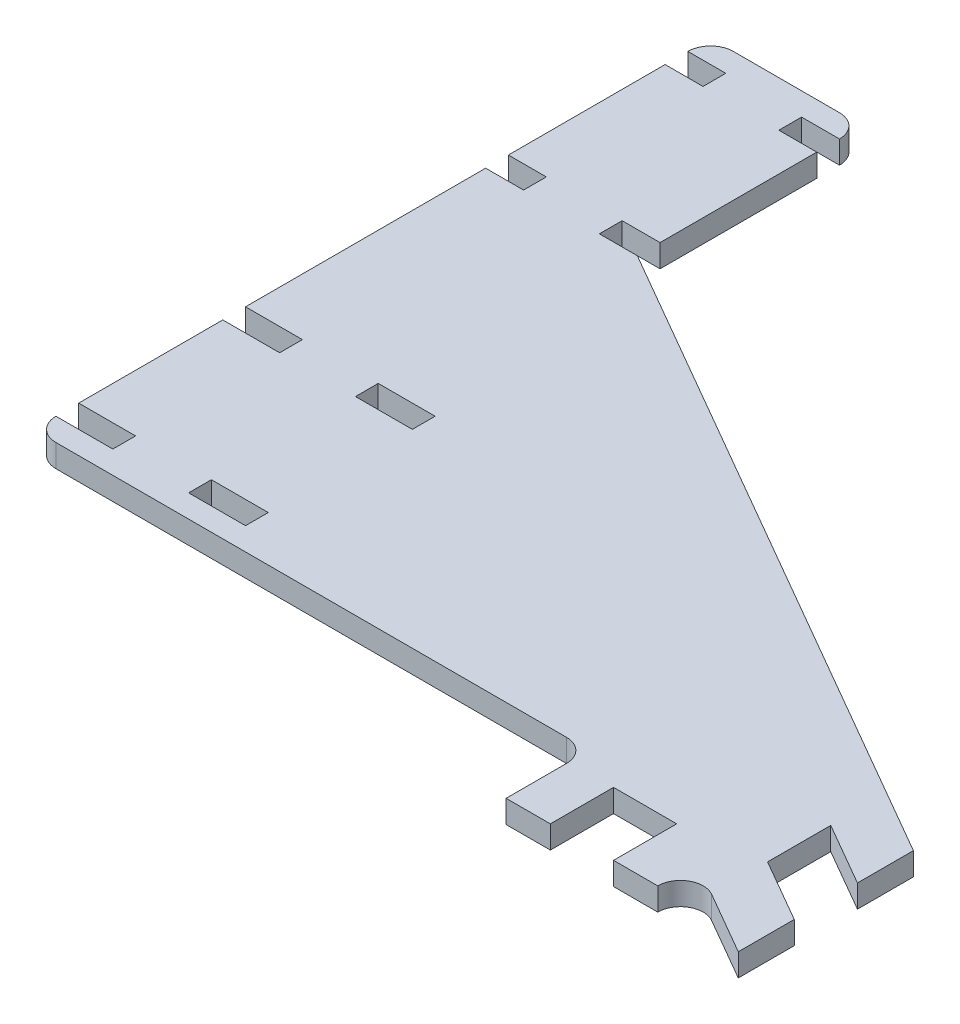
SolidWorks part; units mm, degrees
ref_plane "Front Plane" through (0, 0, 0) normal (0, 0, 1) x (1, 0, 0)
ref_plane "Top Plane" through (0, 0, 0) normal (0, 1, 0) x (1, 0, 0)
ref_plane "Right Plane" through (0, 0, 0) normal (1, 0, 0) x (0, 0, -1)
sketch "Sketch1" plane through (0, 0, 0) normal (0, 1, 0) x (1, 0, 0)
  line L0 (-363.1089, 480) -> (-363.1089, -480)
  line L1 (-363.1089, -480) -> (-303.1089, -480)
  line L2 (-303.1089, -480) -> (-303.1089, -400)
  line L3 (-303.1089, -400) -> (303.1089, -50)
  line L4 (303.1089, -50) -> (1036.8911, -50)
  line L5 (1036.8911, -50) -> (1036.8911, 50) construction
  line L6 (1036.8911, 50) -> (303.1089, 50)
  line L7 (303.1089, 50) -> (-303.1089, 400)
  line L8 (-303.1089, 400) -> (-303.1089, 480)
  line L9 (-303.1089, 480) -> (-363.1089, 480)
  line L10 (-363.1089, 0) -> (1036.8911, 0) construction
  line L11 (0, 225) -> (0, -225) construction
  line L14 (1036.8911, 50) -> (1066.8911, 50)
  line L15 (1036.8911, 50) -> (1036.8911, -50) construction
  line L16 (1036.8911, -50) -> (1066.8911, -50)
  line L17 (1066.8911, 50) -> (1066.8911, -50)
  dimension "D1" = 960
  dimension "D2" = 60
  dimension "D3" = 100
  dimension "D4" = 1400
  dimension "D5" = 150
  dimension "D6" = 80
  dimension "D7" = 30
extrude "Boss-Extrude1" add sketch "Sketch1" along normal blind 9
sketch "Sketch2" plane through (0, 9, 0) normal (0, 1, 0) x (1, 0, 0)
  line L1 (-363.1089, 480) -> (-303.1089, 480)
  line L2 (-363.1089, 480) -> (-363.1089, 400)
  line L3 (-363.1089, 400) -> (-303.1089, 400)
  line L4 (-303.1089, 480) -> (-303.1089, 400)
  line L5 (-363.1089, -480) -> (-303.1089, -480)
  line L6 (-363.1089, -480) -> (-363.1089, -400)
  line L7 (-363.1089, -400) -> (-303.1089, -400)
  line L8 (-303.1089, -480) -> (-303.1089, -400)
extrude "Boss-Extrude2" add sketch "Sketch2" along normal blind 500
sketch "Sketch3" plane through (0, 0, 0) normal (0, 0, 1) x (1, 0, 0)
  line L0 (-333.1089, 509) -> (-333.1089, 254.2) construction
  line L1 (-363.1089, 509) -> (-303.1089, 509) construction
  line L2 (-333.1089, 254.2) -> (-333.1089, 25) construction
  line L3 (-333.1089, 25) -> (-333.1089, 0) construction
  line L4 (-363.1089, 0) -> (-303.1089, 0) construction
  line L6 (-363.1089, 509) -> (-303.1089, 509)
  line L7 (-363.1089, 509) -> (-363.1089, 9)
  line L8 (-363.1089, 9) -> (-303.1089, 9)
  line L9 (-303.1089, 509) -> (-303.1089, 9)
  circle A0 centre (-333.1089, 254.2) radius 229.2
  circle A1 centre (-333.1089, 254.2) radius 6
  circle A2 centre (-333.1089, 254.2) radius 30
  dimension "D1" = 458.4
  dimension "D3" = 12
  dimension "D2" = 25
extrude "Cut-Extrude1" cut sketch "Sketch3" against normal through all both and the other way through all contours A2 L9 A0 L7 | A0 L9 L6 L7 | A1 region at (-333.1089, 495.8654, 0) region at (-333.1089, 380.1444, 0) region at (-333.1089, 254.2, 0)
sketch "Sketch4" plane through (0, 9, 0) normal (0, 1, 0) x (1, 0, 0)
  line L0 (866.8911, 25) -> (1066.8911, 25)
  line L2 (866.8911, -25) -> (1066.8911, -25)
  line L3 (1066.8911, -25) -> (1066.8911, 25)
  line L4 (866.8911, 0) -> (1066.8911, 0) construction
  line L5 (1066.8911, -50) -> (1066.8911, 50) construction
  circle A0 centre (866.8911, 0) radius 25
  dimension "D1" = 50
  dimension "D2" = 200
extrude "Cut-Extrude2" cut sketch "Sketch4" against normal through all contours L4 A0 L2 | A0 L4 L3 L0 | A0 region at (976.6223, 9, -12.7057) region at (884.0688, 9, -17.1777) region at (976.6223, 9, 12.7057)
sketch "Sketch16" plane through (0, 0, 0) normal (0, 0, 1) x (1, 0, 0)
  line L0 (-359.656, 240.2268) -> (-348.1089, 218.2888)
  line L5 (-348.1089, 218.2888) -> (-348.1089, 24)
  line L7 (-363.1089, 9) -> (-288.1089, 9)
  line L8 (303.1089, 9) -> (-303.1089, 9) construction
  line L9 (-303.1089, 254.2) -> (-303.1089, 24)
  line L10 (-348.1089, 24) -> (-363.1089, 9)
  line L11 (-303.1089, 254.2) -> (-303.1089, 9) construction
  line L12 (-303.1089, 24) -> (-288.1089, 9)
  line L13 (-348.1089, 24) -> (-303.1089, 24) construction
  line L14 (-346.3825, 247.2134) -> (-358.4836, 270.2039)
  line L15 (-319.8353, 261.1866) -> (-331.9364, 284.1771)
  circle A0 centre (-333.1089, 254.2) radius 15
  circle A1 centre (-333.1089, 254.2) radius 30
  arc A2 (-303.1089, 254.2) -> (-363.1089, 254.2) centre (-333.1089, 254.2) ccw construction
  circle A3 centre (-360.6089, 215.2) radius 12.5 construction
  dimension "D1" = 30
  dimension "D4" = 25
  dimension "D2" = 45
  dimension "D3" = 45
extrude "Boss-Extrude8" add sketch "Sketch16" along normal blind 305 and the other way blind 305 contours A1 L0 L5 L10 L7 L12 L9 | A1 L15 A0 L14 region at (-325.4564, 117.1914, 0) region at (-362.2383, 255.3393, 0)
sketch "Sketch17" plane through (0, 0, 0) normal (1, 0, 0) x (0, 0, -1)
  line L1 (230, 309) -> (-230, 309)
  line L2 (230, 309) -> (230, 9)
  line L3 (230, 9) -> (-230, 9)
  line L4 (-230, 309) -> (-230, 9)
  line L5 (0, 0) -> (0, 309) construction
  line L6 (480, 0) -> (-480, 0) construction
  dimension "D1" = 460
  dimension "D2" = 9
  dimension "D3" = 300
extrude "Cut-Extrude9" cut sketch "Sketch17" against normal through all
sketch "Sketch7" plane through (0, 0, 0) normal (1, 0, 0) x (0, 0, -1)
  line L1 (480, 284.2) -> (230, 284.2)
  line L2 (480, 284.2) -> (480, 9)
  line L3 (480, 9) -> (230, 9)
  line L4 (230, 284.2) -> (230, 9)
  line L5 (230, 218.2888) -> (230, 24) construction
  line L6 (471, 146.6) -> (444.5, 146.6) construction
  line L7 (480, 284.2) -> (471, 284.2)
  line L8 (480, 284.2) -> (480, 9)
  line L9 (480, 9) -> (471, 9)
  line L10 (471, 284.2) -> (471, 9)
  line L11 (400, 9) -> (409, 9)
  line L12 (400, 9) -> (400, 284.2)
  line L13 (400, 284.2) -> (409, 284.2)
  line L14 (409, 9) -> (409, 284.2)
  line L15 (444.5, 284.2) -> (435.5, 284.2)
  line L16 (444.5, 284.2) -> (444.5, 9)
  line L17 (444.5, 9) -> (435.5, 9)
  line L18 (435.5, 284.2) -> (435.5, 9)
  line L19 (444.5, 146.6) -> (435.5, 146.6) construction
  line L20 (435.5, 146.6) -> (409, 146.6) construction
  line L22 (0, 274.5241) -> (0, -136.9768) construction
  line L23 (-435.5, 146.6) -> (-409, 146.6) construction
  line L24 (305, 284.2) -> (296, 284.2)
  line L25 (305, 284.2) -> (305, 9)
  line L26 (305, 9) -> (296, 9)
  line L27 (296, 284.2) -> (296, 9)
  line L28 (239, 9) -> (230, 9)
  line L29 (239, 9) -> (239, 284.2)
  line L30 (239, 284.2) -> (230, 284.2)
  line L31 (230, 9) -> (230, 284.2)
  line L32 (-444.5, 146.6) -> (-435.5, 146.6) construction
  line L33 (-471, 146.6) -> (-444.5, 146.6) construction
  line L34 (-230, 9) -> (-230, 284.2)
  line L35 (-239, 284.2) -> (-230, 284.2)
  line L36 (-239, 9) -> (-239, 284.2)
  line L37 (-239, 9) -> (-230, 9)
  line L38 (-296, 284.2) -> (-296, 9)
  line L39 (-305, 9) -> (-296, 9)
  line L40 (-305, 284.2) -> (-305, 9)
  line L41 (-305, 284.2) -> (-296, 284.2)
  line L42 (-435.5, 284.2) -> (-435.5, 9)
  line L43 (-444.5, 9) -> (-435.5, 9)
  line L44 (-444.5, 284.2) -> (-444.5, 9)
  line L45 (-444.5, 284.2) -> (-435.5, 284.2)
  line L46 (-409, 9) -> (-409, 284.2)
  line L47 (-400, 284.2) -> (-409, 284.2)
  line L48 (-400, 9) -> (-400, 284.2)
  line L49 (-400, 9) -> (-409, 9)
  line L50 (-471, 284.2) -> (-471, 9)
  line L51 (-480, 9) -> (-471, 9)
  line L52 (-480, 284.2) -> (-480, 9)
  line L53 (-480, 284.2) -> (-471, 284.2)
  line L54 (-230, 284.2) -> (-230, 9)
  line L55 (-480, 9) -> (-230, 9)
  line L56 (-480, 284.2) -> (-480, 9)
  line L57 (-480, 284.2) -> (-230, 284.2)
  line L58 (305, 218.2888) -> (305, 24) construction
  dimension "D1" = 9
  dimension "D2" = 9
  dimension "D3" = 9
  dimension "D4" = 9
  dimension "D5" = 9
extrude "Cut-Extrude4" cut sketch "Sketch7" against normal through all both and the other way through all contours L1 L16 L3 L10 | L18 L1 L14 L3 | L29 L3 L27 L1 | L57 L38 L55 L36 | L57 L42 L55 L46 | L57 L50 L55 L44 | L1 L18 L3 L16 | L45 L44 L43 L42 region at (0, 146.6, -457.75) region at (0, 146.6, -440) region at (0, 146.6, -422.25) region at (0, 146.6, -267.5) region at (0, 146.6, 267.5) region at (0, 146.6, 422.25) region at (0, 146.6, 440) region at (0, 146.6, 457.75)
sketch "Sketch10" plane through (0, 9, 0) normal (0, 1, 0) x (1, 0, 0)
  line L0 (-363.1089, 221) -> (-113.0718, 221)
  line L2 (-113.0718, 221) -> (269.7114, 0)
  line L3 (269.7114, 0) -> (-113.0718, -221)
  line L4 (-113.0718, -221) -> (-363.1089, -221)
  line L5 (-363.1089, -221) -> (-363.1089, 221)
  line L6 (0, 0) -> (269.7114, 0) construction
  line L7 (-363.1089, 0) -> (0, 0) construction
  line L8 (-113.0718, -221) -> (-113.0718, 221) construction
  line L9 (303.1089, 50) -> (-303.1089, 400) construction
  line L10 (-363.1089, -230) -> (-363.1089, 230) construction
  line L11 (303.1089, 50) -> (337.7499, 30)
  line L12 (337.7499, 30) -> (806.8911, 30)
  line L13 (806.8911, 30) -> (841.5321, 50)
  line L14 (1066.8911, 50) -> (303.1089, 50) construction
  line L15 (841.5321, 50) -> (303.1089, 50)
  line L16 (303.1089, -50) -> (337.7499, -30)
  line L17 (337.7499, -30) -> (806.8911, -30)
  line L18 (806.8911, -30) -> (841.5321, -50)
  line L19 (303.1089, -50) -> (1066.8911, -50) construction
  line L20 (841.5321, -50) -> (303.1089, -50)
  line L21 (337.7499, -30) -> (337.7499, 30) construction
  line L22 (269.7114, 0) -> (337.7499, 0) construction
  line L23 (806.8911, 30) -> (806.8911, -30) construction
  line L24 (-303.1089, -400) -> (303.1089, -50) construction
  line L25 (841.5321, 50) -> (841.5321, -50) construction
  line L27 (-363.1089, 230) -> (-288.1089, 230) construction
  line L28 (-363.1089, -230) -> (-288.1089, -230) construction
  arc A0 (866.8911, 25) -> (866.8911, -25) centre (866.8911, 0) ccw construction
  dimension "D1" = 60
  dimension "D2" = 30
  dimension "D3" = 60
  dimension "D4" = 60
  dimension "D5" = 9
  dimension "D6" = 9
extrude "Cut-Extrude6" cut sketch "Sketch10" against normal through all
sketch "Sketch11" plane through (-363.1089, 0, 0) normal (-1, 0, 0) x (0, 0, 1)
  line L0 (-480, 254.2) -> (-480, 0) construction
  line L1 (-480, 224.2) -> (-400, 224.2)
  line L2 (-480, 224.2) -> (-480, 215.2)
  line L3 (-480, 215.2) -> (-400, 215.2)
  line L4 (-400, 224.2) -> (-400, 215.2)
  line L5 (-400, 254.2) -> (-400, 9) construction
  line L6 (400, 254.2) -> (400, 9) construction
  line L7 (400, 224.2) -> (480, 224.2)
  line L8 (400, 224.2) -> (400, 215.2)
  line L9 (400, 215.2) -> (480, 215.2)
  line L10 (480, 224.2) -> (480, 215.2)
  line L11 (480, 254.2) -> (480, 0) construction
  line L12 (-400, 224.2) -> (400, 224.2) construction
  line L13 (400, 215.2) -> (-400, 215.2) construction
  line L14 (-400, 284.2) -> (-409, 284.2) construction
  dimension "D1" = 9
  dimension "D2" = 60
extrude "Boss-Extrude5" add sketch "Sketch11" against normal up to surface (60 mm away) up to face at (-303.1089, 115.9778, 435.5556)
sketch "Sketch18" plane through (-348.1089, 0, 0) normal (-1, 0, 0) x (0, 0, 1)
  line L0 (-230, 218.2888) -> (-230, 24) construction
  line L1 (-305, 218.2888) -> (-230, 218.2888)
  line L2 (-305, 218.2888) -> (-305, 209.2888)
  line L3 (-305, 209.2888) -> (-230, 209.2888)
  line L4 (-230, 218.2888) -> (-230, 209.2888)
  line L5 (230, 24) -> (230, 218.2888) construction
  line L6 (305, 218.2888) -> (230, 218.2888)
  line L7 (305, 218.2888) -> (305, 209.2888)
  line L8 (305, 209.2888) -> (230, 209.2888)
  line L9 (230, 218.2888) -> (230, 209.2888)
  dimension "D1" = 9
  dimension "D2" = 9
extrude "Boss-Extrude9" add sketch "Sketch18" against normal up to surface (45 mm away) up to face at (-303.1089, 139.1, -234.5)
sketch "Sketch12" plane through (0, 9, 0) normal (0, 1, 0) x (1, 0, 0)
  line L0 (-363.1089, -480) -> (-303.1089, -480) construction
  line L1 (-363.1089, 480) -> (-303.1089, 480)
  line L2 (-363.1089, 480) -> (-363.1089, 489)
  line L3 (-363.1089, 489) -> (-303.1089, 489)
  line L4 (-303.1089, 480) -> (-303.1089, 489)
  line L5 (-363.1089, -480) -> (-303.1089, -480)
  line L6 (-363.1089, -480) -> (-363.1089, -489)
  line L7 (-363.1089, -489) -> (-303.1089, -489)
  line L8 (-303.1089, -480) -> (-303.1089, -489)
  dimension "D1" = 9
  dimension "D2" = 9
extrude "Boss-Extrude6" add sketch "Sketch12" against normal blind 9
fillet "Fillet3" radius 9 27 edges at (-303.1089, 4.5, -489) (-363.1089, 4.5, -489) (-363.1089, 4.5, -221) (-363.1089, 4.5, 221) (-363.1089, 4.5, 489) (-303.1089, 4.5, 489) (841.5321, 4.5, 50) (806.8911, 4.5, 30) (841.5321, 4.5, -50) (806.8911, 4.5, -30) (337.7499, 4.5, -30) (337.7499, 4.5, 30) (269.7114, 4.5, 0) (-113.0718, 4.5, 221) (-113.0718, 4.5, -221) (-303.1089, 24, -234.5) (-303.1089, 24, -300.5) (-303.1089, 24, 234.5) (-303.1089, 24, 300.5) (-348.1089, 24, 234.5) (-348.1089, 24, 300.5) (-348.1089, 24, -234.5) (-348.1089, 24, -300.5) (1066.8911, 4.5, 50) (1066.8911, 4.5, 25) (1066.8911, 4.5, -25) (1066.8911, 4.5, -50)
sketch "Sketch15" plane through (0, 9, 0) normal (0, 1, 0) x (1, 0, 0)
  line L0 (-83.154, 230) -> (-83.154, -230)
  line L1 (-113.154, 230) -> (-113.154, 220.6933) construction
  line L2 (-363.1089, 230) -> (-288.1089, 230) construction
  line L4 (-83.154, -230) -> (-143.154, -230)
  line L5 (-143.154, -230) -> (-143.154, 230)
  line L6 (-143.154, 230) -> (-83.154, 230)
  line L7 (0, 0) -> (-83.154, 0) construction
  arc A0 (-110.9833, 219.7942) -> (-115.4833, 221) centre (-115.4833, 212) ccw construction
  dimension "D1" = 60
extrude "Boss-Extrude7" add sketch "Sketch15" against normal blind 9
fillet "Fillet4" radius 9 4 edges at (-83.154, 4.5, -203.7269) (-83.154, 4.5, 203.7269) (-143.154, 4.5, 221) (-143.154, 4.5, -221)
sketch "Sketch20" plane through (0, 9, 0) normal (0, 1, 0) x (1, 0, 0)
  line L0 (-348.1089, 480) -> (-348.1089, 400)
  line L1 (-363.1089, 480) -> (-303.1089, 480)
  line L2 (-363.1089, 480) -> (-363.1089, 471)
  line L3 (-363.1089, 471) -> (-303.1089, 471)
  line L4 (-303.1089, 480) -> (-303.1089, 471)
  line L5 (-363.1089, 409) -> (-303.1089, 409)
  line L6 (-363.1089, 409) -> (-363.1089, 400)
  line L7 (-363.1089, 400) -> (-303.1089, 400)
  line L8 (-303.1089, 409) -> (-303.1089, 400)
  line L9 (-363.1089, 305) -> (-288.1089, 305)
  line L10 (-363.1089, 305) -> (-363.1089, 296)
  line L11 (-363.1089, 296) -> (-288.1089, 296)
  line L12 (-288.1089, 305) -> (-288.1089, 296)
  line L13 (-363.1089, 239) -> (-288.1089, 239)
  line L14 (-363.1089, 239) -> (-363.1089, 230)
  line L15 (-363.1089, 230) -> (-288.1089, 230)
  line L16 (-288.1089, 239) -> (-288.1089, 230)
  line L17 (-318.1089, 480) -> (-318.1089, 400)
  line L18 (-363.1089, 440) -> (-348.1089, 440) construction
  line L19 (-363.1089, 409) -> (-363.1089, 471) construction
  line L20 (-348.1089, 440) -> (-318.1089, 440) construction
  line L21 (-318.1089, 440) -> (-303.1089, 440) construction
  line L22 (-303.1089, 471) -> (-303.1089, 409) construction
  line L23 (-340.6089, 305) -> (-340.6089, 230)
  line L24 (-310.6089, 305) -> (-310.6089, 230)
  line L25 (-288.1089, 296) -> (-288.1089, 239) construction
  line L26 (-363.1089, 267.5) -> (-340.6089, 267.5) construction
  line L27 (-363.1089, 296) -> (-363.1089, 239) construction
  line L28 (-340.6089, 267.5) -> (-310.6089, 267.5) construction
  line L29 (-310.6089, 267.5) -> (-288.1089, 267.5) construction
  line L30 (-512.4702, 0) -> (462.9433, 0) construction
  line L31 (-310.6089, -267.5) -> (-288.1089, -267.5) construction
  line L32 (-340.6089, -267.5) -> (-310.6089, -267.5) construction
  line L33 (-363.1089, -267.5) -> (-340.6089, -267.5) construction
  line L34 (-288.1089, -296) -> (-288.1089, -239) construction
  line L35 (-318.1089, -440) -> (-303.1089, -440) construction
  line L36 (-348.1089, -440) -> (-318.1089, -440) construction
  line L37 (-363.1089, -440) -> (-348.1089, -440) construction
  line L38 (-310.6089, -305) -> (-310.6089, -230)
  line L39 (-340.6089, -305) -> (-340.6089, -230)
  line L40 (-318.1089, -480) -> (-318.1089, -400)
  line L41 (-288.1089, -239) -> (-288.1089, -230)
  line L42 (-363.1089, -230) -> (-288.1089, -230)
  line L43 (-363.1089, -239) -> (-363.1089, -230)
  line L44 (-363.1089, -239) -> (-288.1089, -239)
  line L45 (-288.1089, -305) -> (-288.1089, -296)
  line L46 (-363.1089, -296) -> (-288.1089, -296)
  line L47 (-363.1089, -305) -> (-363.1089, -296)
  line L48 (-363.1089, -305) -> (-288.1089, -305)
  line L49 (-303.1089, -409) -> (-303.1089, -400)
  line L50 (-363.1089, -400) -> (-303.1089, -400)
  line L51 (-363.1089, -409) -> (-363.1089, -400)
  line L52 (-363.1089, -409) -> (-303.1089, -409)
  line L53 (-303.1089, -480) -> (-303.1089, -471)
  line L54 (-363.1089, -471) -> (-303.1089, -471)
  line L55 (-363.1089, -480) -> (-363.1089, -471)
  line L56 (-363.1089, -480) -> (-303.1089, -480)
  line L57 (-348.1089, -480) -> (-348.1089, -400)
  dimension "D1" = 30
  dimension "D2" = 30
sketch "Sketch21" plane through (0, 9, 0) normal (0, 1, 0) x (1, 0, 0)
  line L0 (1066.8911, 34) -> (1066.8911, 41) construction
  line L1 (-363.1089, 489) -> (1066.8911, 489)
  line L2 (-363.1089, 489) -> (-363.1089, -489)
  line L3 (-363.1089, -489) -> (1066.8911, -489)
  line L4 (1066.8911, 489) -> (1066.8911, -489)
  line L5 (-354.1089, -489) -> (-312.1089, -489) construction
  line L6 (-363.1089, -305) -> (-363.1089, -400) construction
  line L7 (-312.1089, 489) -> (-354.1089, 489) construction
extrude "Cut-Extrude11" cut sketch "Sketch20" against normal through all both and the other way through all contours L56 L57 L54 L55 | L40 L56 L53 L54 | L52 L57 L50 L51 | L40 L52 L49 L50 | L47 L48 L39 L46 | L38 L48 L45 L46 | L38 L44 L41 L42 | L43 L44 L39 L42 | L23 L13 L14 L15 | L13 L24 L15 L16 | L9 L24 L11 L12 | L23 L9 L10 L11 | L6 L7 L0 L5 | L5 L17 L7 L8 | L1 L17 L3 L4 | L2 L3 L0 L1 region at (-355.6089, 9, -475.5) region at (-310.6089, 9, -475.5) region at (-355.6089, 9, -404.5) region at (-310.6089, 9, -404.5) region at (-351.8589, 9, -300.5) region at (-299.3589, 9, -300.5) region at (-351.8589, 9, -234.5) region at (-299.3589, 9, -234.5) region at (-299.3589, 9, 300.5) region at (-351.8589, 9, 300.5) region at (-299.3589, 9, 234.5) region at (-351.8589, 9, 234.5) region at (-310.6089, 9, 475.5) region at (-355.6089, 9, 475.5) region at (-310.6089, 9, 404.5) region at (-355.6089, 9, 404.5)
extrude "Cut-Extrude12" cut sketch "Sketch21" along normal through all
sketch "Sketch22" plane through (0, 9, 0) normal (0, 1, 0) x (1, 0, 0)
  line L0 (1066.8911, 34) -> (1066.8911, 41) construction
  line L1 (-363.1089, -489) -> (1066.8911, -489)
  line L2 (-363.1089, -489) -> (-363.1089, 489)
  line L3 (-363.1089, 489) -> (1066.8911, 489)
  line L4 (1066.8911, -489) -> (1066.8911, 489)
  line L5 (-312.1089, 489) -> (-354.1089, 489) construction
  line L6 (-363.1089, 471) -> (-363.1089, 409) construction
  line L7 (-354.1089, -489) -> (-312.1089, -489) construction
  line L8 (-83.154, 188.1385) -> (-143.154, 188.1385)
  line L9 (-143.154, 212) -> (-143.154, -212) construction
  line L10 (-113.154, 188.1385) -> (-113.154, 213.1385) construction
  line L11 (-69.654, 195.9327) -> (-69.654, 265.2147)
  line L12 (-125.654, 188.1385) -> (-100.654, 188.1385)
  line L13 (256.2114, 7.7942) -> (286.2114, 59.7558)
  line L14 (256.2114, 7.7942) -> (231.2114, 22.228)
  line L15 (231.2114, 22.228) -> (239.9614, 37.3834)
  line L16 (335.6615, 31.2058) -> (-303.1089, 400) construction
  line L17 (256.2114, 7.7942) -> (256.2114, -7.7942)
  line L18 (-69.654, 265.2147) -> (-297.5196, 489)
  line L19 (-143.154, 188.1385) -> (-363.1089, 188.1385)
  line L20 (340.1615, 88.1184) -> (-69.654, 265.2147)
  line L21 (340.1615, 88.1184) -> (1066.8911, 88.1184)
  line L22 (194.4241, 7.7942) -> (-83.154, 188.1385)
  line L23 (-69.654, 195.9327) -> (-83.154, 188.1385)
  line L24 (-125.654, 188.1385) -> (-125.654, 213.1385)
  line L25 (-125.654, 213.1385) -> (-100.654, 213.1385)
  line L26 (-100.654, 188.1385) -> (-100.654, 213.1385)
  line L27 (-69.654, 195.9327) -> (-44.654, 181.4989)
  line L28 (256.2114, 7.7942) -> (-69.654, 195.9327) construction
  line L29 (-44.654, 181.4989) -> (-44.654, 203.64)
  line L30 (-44.654, 203.64) -> (-69.654, 218.0737)
  line L32 (-69.654, 265.2147) -> (-44.654, 250.781)
  line L33 (-44.654, 250.781) -> (-44.654, 228.64)
  line L34 (-44.654, 228.64) -> (-69.654, 243.0737)
  line L35 (-44.654, 203.64) -> (-44.654, 228.64)
  line L36 (239.9614, 37.3834) -> (264.9614, 22.9497)
  line L37 (239.9614, 37.3834) -> (252.4614, 59.0341)
  line L38 (252.4614, 59.0341) -> (277.4614, 44.6003)
  line L39 (252.4614, 59.0341) -> (261.2114, 74.1895)
  line L40 (261.2114, 74.1895) -> (286.2114, 59.7558)
  line L41 (194.4241, 7.7942) -> (256.2114, 7.7942)
  line L42 (286.2114, 59.7558) -> (340.1615, 88.1184)
  line L43 (-181.378, 0) -> (-33.8367, 0) construction
  line L44 (-113.154, -188.1385) -> (-113.154, -213.1385) construction
  line L45 (286.2114, -59.7558) -> (340.1615, -88.1184)
  line L46 (194.4241, -7.7942) -> (256.2114, -7.7942)
  line L47 (261.2114, -74.1895) -> (286.2114, -59.7558)
  line L48 (252.4614, -59.0341) -> (261.2114, -74.1895)
  line L49 (252.4614, -59.0341) -> (277.4614, -44.6003)
  line L50 (239.9614, -37.3834) -> (252.4614, -59.0341)
  line L51 (239.9614, -37.3834) -> (264.9614, -22.9497)
  line L52 (-44.654, -203.64) -> (-44.654, -228.64)
  line L53 (-44.654, -228.64) -> (-69.654, -243.0737)
  line L54 (-44.654, -250.781) -> (-44.654, -228.64)
  line L55 (-69.654, -265.2147) -> (-44.654, -250.781)
  line L56 (-44.654, -203.64) -> (-69.654, -218.0737)
  line L57 (-44.654, -181.4989) -> (-44.654, -203.64)
  line L58 (-69.654, -195.9327) -> (-44.654, -181.4989)
  line L59 (-100.654, -188.1385) -> (-100.654, -213.1385)
  line L60 (-125.654, -213.1385) -> (-100.654, -213.1385)
  line L61 (-125.654, -188.1385) -> (-125.654, -213.1385)
  line L62 (-69.654, -195.9327) -> (-83.154, -188.1385)
  line L63 (194.4241, -7.7942) -> (-83.154, -188.1385)
  line L64 (340.1615, -88.1184) -> (1066.8911, -88.1184)
  line L65 (340.1615, -88.1184) -> (-69.654, -265.2147)
  line L66 (-143.154, -188.1385) -> (-363.1089, -188.1385)
  line L67 (-69.654, -265.2147) -> (-297.5196, -489)
  line L68 (231.2114, -22.228) -> (239.9614, -37.3834)
  line L69 (256.2114, -7.7942) -> (231.2114, -22.228)
  line L70 (256.2114, -7.7942) -> (286.2114, -59.7558)
  line L71 (-125.654, -188.1385) -> (-100.654, -188.1385)
  line L72 (-69.654, -195.9327) -> (-69.654, -265.2147)
  line L73 (-83.154, -188.1385) -> (-143.154, -188.1385)
  line L74 (-363.1089, -489) -> (1066.8911, -489)
  line L75 (194.4241, -7.7942) -> (194.4241, 7.7942)
  dimension "D1" = 25
  dimension "D2" = 25
  dimension "D3" = 25
  dimension "D4" = 25
  dimension "D5" = 25
  dimension "D6" = 25
extrude "Cut-Extrude15" cut sketch "Sketch22" against normal through all contours L63 L75 L22 L8 L19 L2 L66 L73 L71 | L40 L42 L20 L32 L33 L35 L29 L27 L23 L22 L41 L14 L15 L37 L39 | L30 L35 L34 L11 | L8 L26 L25 L24 | L24 L12 L26 L25 region at (-142.7114, 9, 0) region at (-113.154, 9, -200.6385) region at (122.7349, 9, -124.6322) region at (-57.154, 9, -223.3568)
